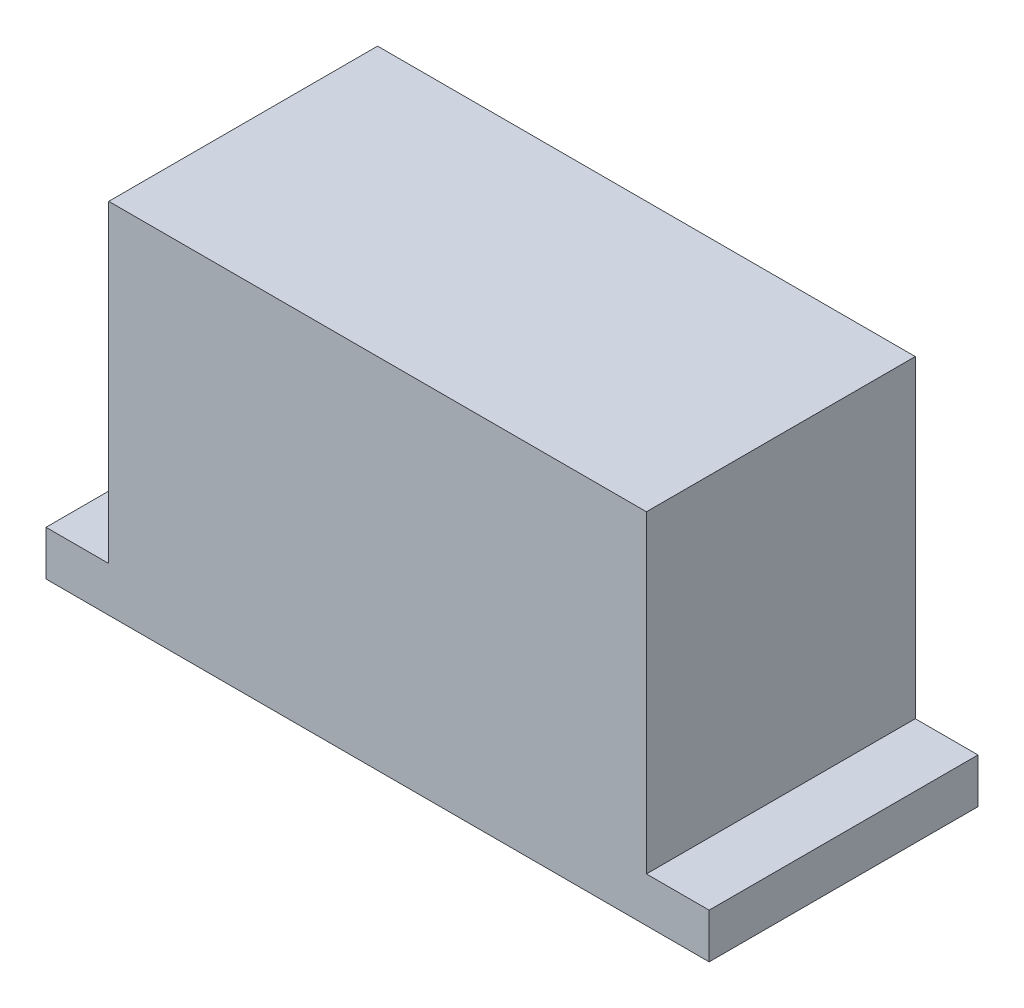
SolidWorks part; units mm, degrees
ref_plane "Front Plane" through (0, 0, 0) normal (0, 0, 1) x (1, 0, 0)
ref_plane "Top Plane" through (0, 0, 0) normal (0, 1, 0) x (1, 0, 0)
ref_plane "Right Plane" through (0, 0, 0) normal (1, 0, 0) x (0, 0, -1)
sketch "Sketch5" plane through (0, 0, 0) normal (0, 1, 0) x (1, 0, 0)
  line L1 (-30, 15) -> (30, 15)
  line L2 (-30, 15) -> (-30, -15)
  line L3 (-30, -15) -> (30, -15)
  line L4 (30, 15) -> (30, -15)
  line L5 (-30, 15) -> (30, -15) construction
  line L6 (-30, -15) -> (30, 15) construction
  point P0 (0, 0)
  dimension "D1" = 30
  dimension "D2" = 60
extrude "Boss-Extrude3" add sketch "Sketch5" along normal blind 40
sketch "Sketch6" plane through (0, 0, 15) normal (0, 0, 1) x (1, 0, 0)
  line L0 (0, 20) -> (-20, 20) construction
  line L3 (-25, 35) -> (25, 35)
  line L4 (-25, 35) -> (-25, 5)
  line L5 (-25, 5) -> (25, 5)
  line L6 (25, 35) -> (25, 5)
  line L7 (-25, 35) -> (25, 5) construction
  line L8 (-25, 5) -> (25, 35) construction
  line L10 (-20, 20) -> (-20, 30) construction
  line L12 (0, 20) -> (20, 20) construction
  line L13 (20, 20) -> (20, 10) construction
  line L14 (-20, 20) -> (-20, 10) construction
  line L15 (20, 20) -> (20, 30) construction
  line L16 (-30, 40) -> (-30, 0) construction
  line L17 (-30, 0) -> (30, 0) construction
  line L18 (-30, 40) -> (30, 40) construction
  point P8 (0, 20)
  dimension "D1" = 50
  dimension "D2" = 30
sketch "Sketch7" plane through (0, 0, -15) normal (0, 0, -1) x (-1, 0, 0)
  line L3 (-20, 10) -> (20, 10)
  line L4 (-20, 10) -> (-20, 30)
  line L5 (-20, 30) -> (20, 30)
  line L6 (20, 10) -> (20, 30)
  line L7 (-20, 10) -> (20, 30) construction
  line L8 (-20, 30) -> (20, 10) construction
  point P8 (0, 20)
  dimension "D1" = 20
  dimension "D2" = 40
extrude "Cut-Extrude1" cut sketch "Sketch7" against normal blind 15
fillet "Fillet1" radius 3 1 edges at (20, 10, -7.5)
fillet "Fillet2" radius 3 1 edges at (-20, 10, -7.5)
fillet "Fillet3" radius 3 1 edges at (-20, 30, -7.5)
fillet "Fillet4" radius 3 1 edges at (20, 30, -7.5)
sketch "Sketch8" plane through (0, 10, 0) normal (0, 1, 0) x (1, 0, 0)
  line L0 (0, 15) -> (0, 0) construction
  line L1 (17, 15) -> (-17, 15) construction
  dimension "D1" = 15
sketch "Sketch9" plane through (-30, 0, 0) normal (-1, 0, 0) x (0, 0, 1)
  line L0 (15, 40) -> (15, 0) construction
  line L1 (-15, 0) -> (15, 0)
  line L2 (-15, 0) -> (-15, 5)
  line L3 (-15, 5) -> (15, 5)
  line L4 (15, 0) -> (15, 5)
extrude "Boss-Extrude4" add sketch "Sketch9" along normal blind 7
sketch "Sketch10" plane through (30, 0, 0) normal (1, 0, 0) x (0, 0, -1)
  line L0 (15, 40) -> (15, 0) construction
  line L1 (-15, 0) -> (15, 0)
  line L2 (-15, 0) -> (-15, 5)
  line L3 (-15, 5) -> (15, 5)
  line L4 (15, 0) -> (15, 5)
extrude "Boss-Extrude5" add sketch "Sketch10" along normal blind 7
sketch "Sketch11" plane through (-30, 0, 0) normal (-1, 0, 0) x (0, 0, 1)
  line L0 (-15, 40) -> (0, 40) construction
  line L1 (-15, 40) -> (15, 40) construction
  line L2 (0, 40) -> (0, 5) construction
  line L3 (15, 5) -> (-15, 5) construction
  line L4 (0, 40) -> (-15, 5) construction
sketch "Sketch12" plane through (-30, 0, 0) normal (-1, 0, 0) x (0, 0, 1)
  circle A0 centre (-7.5315, 22.7105) radius 2
extrude "Cut-Extrude2" cut sketch "Sketch12" against normal blind 10
sketch "Sketch13" plane through (0, 0, 0) normal (0, -1, 0) x (-1, 0, 0)
  line L0 (-37, 15) -> (37, -15) construction
  line L1 (-37, -15) -> (37, 15) construction
  line L3 (-32, 10) -> (32, 10)
  line L4 (-32, 10) -> (-32, -10)
  line L5 (-32, -10) -> (32, -10)
  line L6 (32, 10) -> (32, -10)
  line L7 (-32, 10) -> (32, -10) construction
  line L8 (-32, -10) -> (32, 10) construction
  point P8 (0, 0)
  dimension "D1" = 64
  dimension "D2" = 20
extrude "Cut-Extrude3" cut sketch "Sketch13" against normal blind 1.5
sketch "Sketch14" plane through (0, 0, -15) normal (0, 0, -1) x (-1, 0, 0)
  line L0 (-30, 40) -> (30, 0) construction
  line L1 (-37, 0) -> (37, 0) construction
  line L2 (30, 40) -> (-30, 0) construction
  line L3 (0, 20) -> (25, 20) construction
  line L4 (25, 20) -> (25, 36) construction
  line L5 (25, 20) -> (25, 4) construction
  line L6 (0, 20) -> (-25, 20) construction
  line L7 (-25, 20) -> (-25, 36) construction
  line L8 (-25, 20) -> (-25, 4) construction
  dimension "D1" = 16
  dimension "D2" = 25
